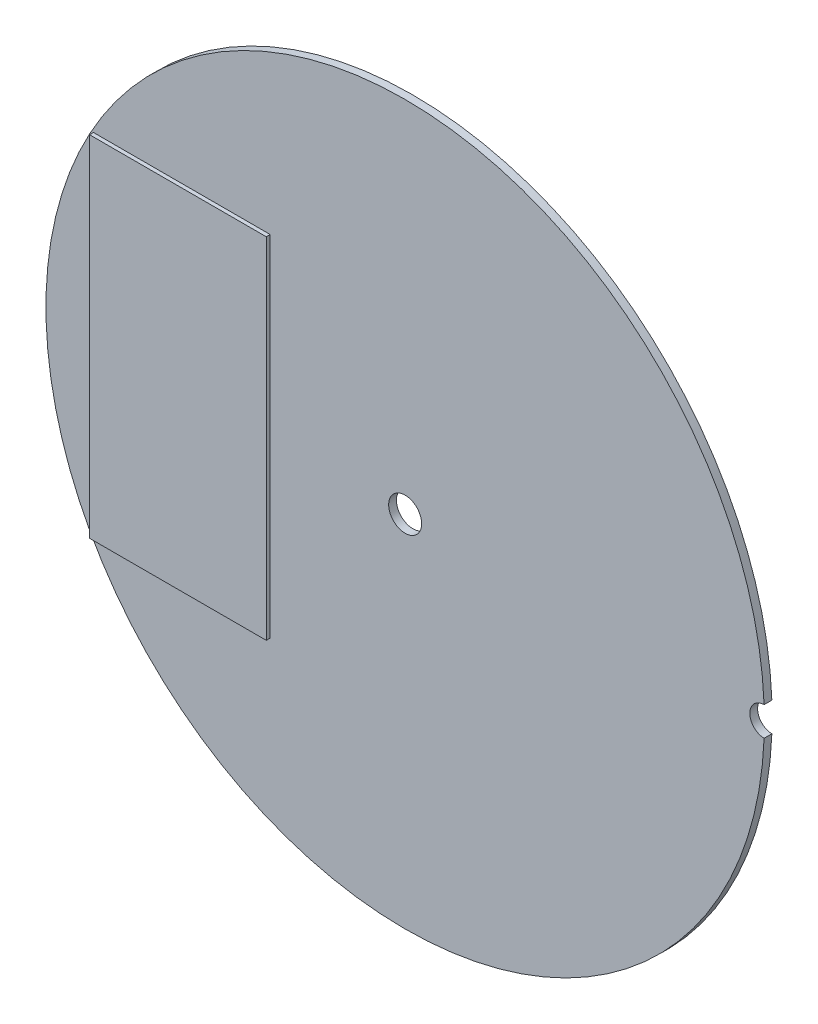
SolidWorks part; units mm, degrees
ref_plane "Plan de face" through (0, 0, 0) normal (0, 0, 1) x (1, 0, 0)
ref_plane "Plan de dessus" through (0, 0, 0) normal (0, 1, 0) x (1, 0, 0)
ref_plane "Plan de droite" through (0, 0, 0) normal (1, 0, 0) x (0, 0, -1)
sketch "Esquisse1" plane through (0, 0, 0) normal (0, 0, 1) x (1, 0, 0)
  line L0 (0, 0) -> (18.5, 0) construction
  line L1 (0, 18.5) -> (0, 0) construction
  line L2 (-6.7, -3.3481) -> (-6.7, 3.3481) construction
  line L3 (-11.5, -4.5) -> (-11.5, 4.5) construction
  line L4 (-14.5, -4.5) -> (-14.5, 4.5)
  line L5 (-8.5, -4.5) -> (-8.5, 4.5)
  line L6 (-11.5, 0) -> (0, 0) construction
  arc A0 (18.4848, 0.7498) -> (18.4848, -0.7498) centre (0, 0) ccw
  arc A2 (18.4848, 0.7498) -> (18.4848, -0.7498) centre (18.5, 0) ccw
  circle A4 centre (0, 0) radius 0.85
  arc A6 (-14.5, -4.5) -> (-8.5, -4.5) centre (-11.5, -4.5) ccw
  arc A7 (-8.5, 4.5) -> (-14.5, 4.5) centre (-11.5, 4.5) ccw
  point P5 (8.234, -1.9)
  point P6 (-7.9, -3)
  point P11 (-11.5, 0)
  point P17 (-12.3842, 0)
  point P20 (-11.5, 0)
  dimension "D1" = 37
  dimension "D6" = 6
  dimension "D8" = 1.5
  dimension "D10" = 1.7
  dimension "D7" = 9
  dimension "D2" = 1.9
  dimension "D3" = 3
  dimension "D4" = 7.9
  dimension "D5" = 8.234
  dimension "D9" = 18.5
  dimension "D11" = 1.8
extrude "Boss.-Extru.1" add sketch "Esquisse1" along normal blind 0.4
sketch "Esquisse2" plane through (0, 0, 0.4) normal (0, 0, 1) x (1, 0, 0)
  line L0 (-11.5, -7.5) -> (-11.5, 7.5) construction
  line L1 (-16.05, 9) -> (-6.95, 9)
  line L2 (-16.05, 9) -> (-16.05, -9)
  line L3 (-16.05, -9) -> (-6.95, -9)
  line L4 (-6.95, 9) -> (-6.95, -9)
  line L5 (-16.05, 9) -> (-6.95, -9) construction
  line L6 (-16.05, -9) -> (-6.95, 9) construction
  arc A0 (-14.5, -4.5) -> (-8.5, -4.5) centre (-11.5, -4.5) ccw construction
  arc A1 (-8.5, 4.5) -> (-14.5, 4.5) centre (-11.5, 4.5) ccw construction
  point P0 (-11.5, 0)
  point P13 (-11.7, 0)
  dimension "D1" = 9.1
  dimension "D2" = 18
extrude "Boss.-Extru.2" add sketch "Esquisse2" along normal blind 0.2
